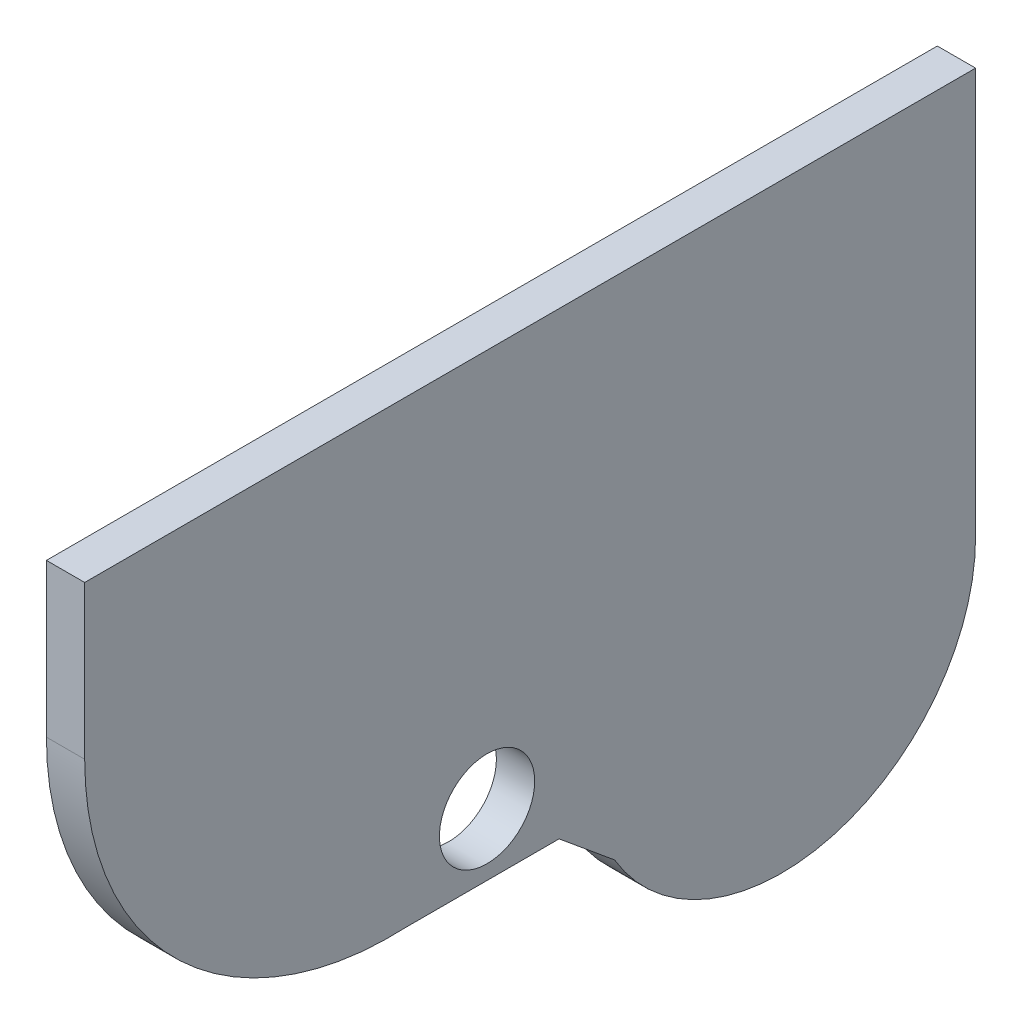
SolidWorks part; units mm, degrees
ref_plane "Front Plane" through (0, 0, 0) normal (0, 0, 1) x (1, 0, 0)
ref_plane "Top Plane" through (0, 0, 0) normal (0, 1, 0) x (1, 0, 0)
ref_plane "Right Plane" through (0, 0, 0) normal (1, 0, 0) x (0, 0, -1)
sketch "Sketch1" plane through (0, 0, 0) normal (1, 0, 0) x (0, 0, -1)
  line L0 (-53.2162, 59.5847) -> (94.596, 59.5847)
  line L1 (94.596, 59.5847) -> (94.596, -7.7934)
  line L2 (-53.2162, 59.5847) -> (-53.2162, 34.1847)
  line L4 (0.0988, -16.6153) -> (25.4988, -16.6153)
  arc A0 (94.596, -7.7934) -> (34.6979, -24.2408) centre (62.3888, -7.7934) cw
  arc A1 (-53.2162, 34.1847) -> (0.0988, -16.6153) centre (-2.3568, 34.1847) ccw
  circle A2 centre (13.5398, -6.3073) radius 7.9038
  spline S0 degree 1 poles (25.4988, -16.6153) (34.6979, -24.2408) knots 0 0 1 1
  dimension "D4" = 32.2072
  dimension "D1" = 25.4
  dimension "D2" = 25.4
  dimension "D3" = 76.2
extrude "Boss-Extrude1" add sketch "Sketch1" along normal blind 6.35
